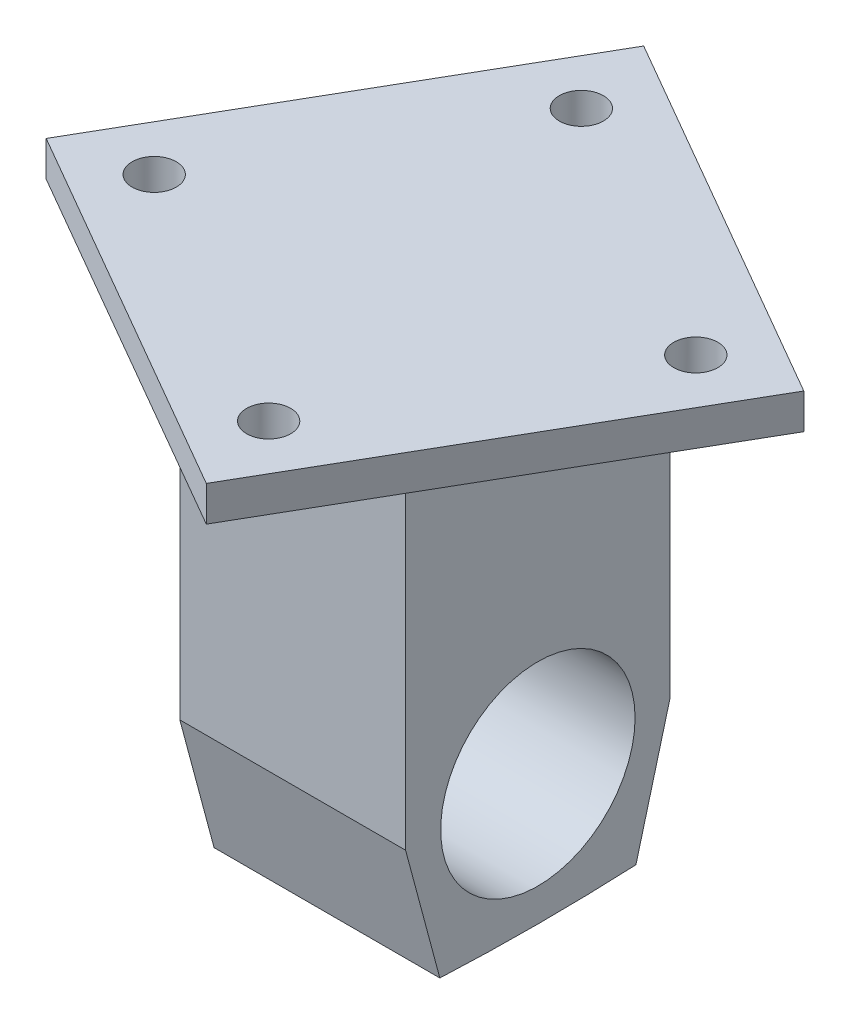
SolidWorks part; units mm, degrees
material "ABS"
ref_plane "Front Plane" through (0, 0, 0) normal (0, 0, 1) x (1, 0, 0)
ref_plane "Top Plane" through (0, 0, 0) normal (0, 1, 0) x (1, 0, 0)
ref_plane "Right Plane" through (0, 0, 0) normal (1, 0, 0) x (0, 0, -1)
sketch "Sketch1" plane through (0, 0, 0) normal (0, 1, 0) x (1, 0, 0)
  line L1 (-16.256, -19.05) -> (16.256, -19.05)
  line L2 (-16.256, -19.05) -> (-16.256, 19.05)
  line L3 (-16.256, 19.05) -> (16.256, 19.05)
  line L4 (16.256, -19.05) -> (16.256, 19.05)
  line L5 (-16.256, -19.05) -> (16.256, 19.05) construction
  line L6 (-16.256, 19.05) -> (16.256, -19.05) construction
  point P0 (0, 0)
extrude "Boss-Extrude1" add sketch "Sketch1" along normal blind 50.292
sketch "Sketch2" plane through (16.256, 0, 0) normal (1, 0, 0) x (0, 0, -1)
  line L0 (-19.05, 0) -> (-14.1195, -18.4009)
  line L1 (19.05, 0) -> (14.1195, -18.4009)
  line L2 (-19.05, 0) -> (19.05, 0)
  line L3 (-19.05, 0) -> (19.05, 0) construction
  arc A1 (14.1195, -18.4009) -> (-14.1195, -18.4009) centre (0, 281.2546) cw
  dimension "D1" = 19.05
  dimension "D2" = 19.05
  dimension "D3" = 75
  dimension "D4" = 75
extrude "Boss-Extrude2" add sketch "Sketch2" against normal up to vertex (32.512 mm away) contours L0 A1 L1 L2 up to point (-16.256, 0, -19.05)
sketch "Sketch3" plane through (16.256, 0, 0) normal (1, 0, 0) x (0, 0, -1)
  circle A0 centre (0, 0) radius 14
extrude "Cut-Extrude1" cut sketch "Sketch3" against normal blind 127 contours A0
sketch "Sketch4" plane through (0, 50.292, 0) normal (0, 1, 0) x (1, 0, 0)
  line L0 (-46.8473, -12.5527) -> (46.8473, 12.5527) construction
  line L5 (13.6389, -50.901) -> (-13.6389, 50.901) construction
  line L6 (43.0243, 11.5283) -> (11.5283, -43.0243)
  line L11 (11.5283, -43.0243) -> (-43.0243, -11.5283)
  line L12 (-43.0243, -11.5283) -> (-11.5283, 43.0243)
  line L13 (-11.5283, 43.0243) -> (43.0243, 11.5283)
  line L14 (11.5283, -43.0243) -> (-11.5283, 43.0243) construction
  line L15 (-43.0243, -11.5283) -> (43.0243, 11.5283) construction
  point P1 (0, 0)
  point P4 (0, 0)
  point P11 (0, 0)
  dimension "D1" = 62.992
  dimension "D2" = 62.992
  dimension "D3" = 0
  dimension "D4" = 0
extrude "Boss-Extrude3" add sketch "Sketch4" along normal blind 5.08
sketch "Sketch5" plane through (0, 55.372, 0) normal (0, 1, 0) x (1, 0, 0)
  line L2 (30.7571, 8.2413) -> (43.0243, 11.5283) construction
  line L3 (8.2413, -30.7571) -> (11.5283, -43.0243) construction
  line L4 (-30.7571, -8.2413) -> (-43.0243, -11.5283) construction
  line L5 (-8.2413, 30.7571) -> (-11.5283, 43.0243) construction
  line L6 (-11.5283, 43.0243) -> (-43.0243, -11.5283) construction
  line L7 (43.0243, 11.5283) -> (-11.5283, 43.0243) construction
  line L8 (-43.0243, -11.5283) -> (11.5283, -43.0243) construction
  circle A0 centre (30.7571, 8.2413) radius 3.175
  circle A1 centre (8.2413, -30.7571) radius 3.175
  circle A2 centre (-8.2413, 30.7571) radius 3.175
  circle A3 centre (-30.7571, -8.2413) radius 3.175
  dimension "D2" = 6.35
  dimension "D4" = 6.35
  dimension "D11" = 6.35
  dimension "D12" = 6.35
  dimension "D1" = 12.7
  dimension "D3" = 45
  dimension "D5" = 12.7
  dimension "D6" = 45
  dimension "D7" = 12.7
  dimension "D8" = 45
  dimension "D9" = 12.7
  dimension "D10" = 45
extrude "Cut-Extrude2" cut sketch "Sketch5" against normal through all
